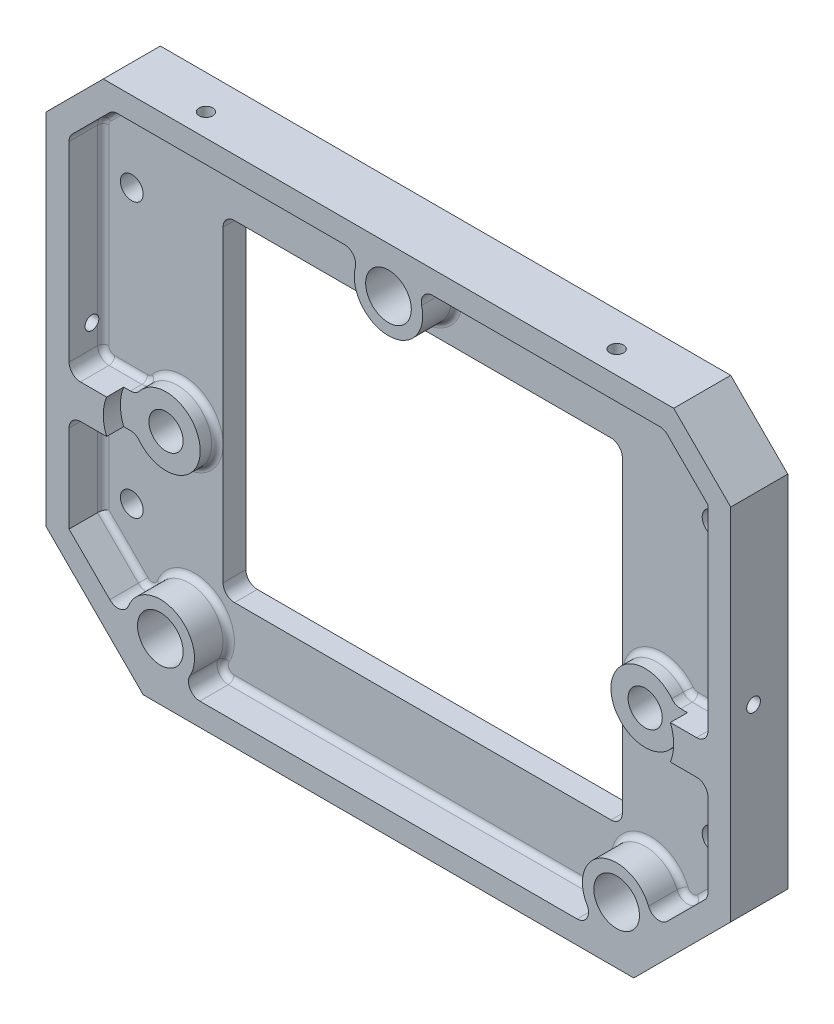
SolidWorks part; units mm, degrees
ref_plane "前视基准面" through (0, 0, 0) normal (0, 0, 1) x (1, 0, 0)
ref_plane "上视基准面" through (0, 0, 0) normal (0, 1, 0) x (1, 0, 0)
ref_plane "右视基准面" through (0, 0, 0) normal (1, 0, 0) x (0, 0, -1)
sketch "草图1" plane through (0, 0, 0) normal (0, 0, 1) x (1, 0, 0)
  line L0 (0, 54.5254) -> (0, -46.9226) construction
  line L1 (77.1188, 0) -> (-86.5987, 0) construction
  line L2 (-30, 25) -> (-18, 25) construction
  line L3 (-18, 25) -> (-18, 1.5) construction
  line L4 (-18, 1.5) -> (-30, 1.5) construction
  line L5 (-30, 1.5) -> (-30, -3.5)
  line L6 (-30, -3.5) -> (-21.5, -12)
  line L7 (-21.5, -12) -> (-15.5, -12)
  line L8 (-15.5, -12) -> (-15.5, 0) construction
  line L9 (-15.5, 0) -> (15.5, 0) construction
  line L10 (-30, 25) -> (-30, 28)
  line L11 (-25, 33) -> (25, 33)
  line L12 (-17.5, 24) -> (-17.5, -3)
  line L13 (-16.5, -4) -> (16.5, -4)
  line L14 (16.5, 25) -> (-16.5, 25)
  line L15 (15.5, -12) -> (15.5, 0) construction
  line L16 (21.5, -12) -> (15.5, -12)
  line L17 (18, 1.5) -> (30, 1.5) construction
  line L18 (30, 1.5) -> (30, -3.5)
  line L19 (18, 25) -> (18, 1.5) construction
  line L20 (30, 25) -> (30, 28)
  line L21 (17.5, 24) -> (17.5, -3)
  line L22 (18, 25) -> (30, 25) construction
  line L23 (21.5, -12) -> (30, -3.5)
  line L24 (-30, 28) -> (-25, 33)
  line L25 (30, 28) -> (25, 33)
  line L26 (-30, 25) -> (-30, 1.5)
  line L27 (30, 25) -> (30, 1.5)
  line L28 (-15.5, -12) -> (15.5, -12)
  circle A0 centre (20, -7) radius 2
  circle A1 centre (12.5, 29) radius 2 construction
  circle A2 centre (0, 29) radius 2
  circle A3 centre (-20, -7) radius 2
  circle A4 centre (-12.5, 29) radius 2 construction
  circle A5 centre (24, 27.5) radius 1 construction
  circle A6 centre (24, -1) radius 1 construction
  circle A7 centre (-24, 27.5) radius 1 construction
  circle A8 centre (-24, -1) radius 1 construction
  circle A9 centre (-21, 7.5) radius 6 construction
  circle A10 centre (-21, 7.5) radius 1.5
  circle A11 centre (21, 7.5) radius 1.5
  arc A12 (-17.5, -3) -> (-16.5, -4) centre (-16.5, -3) ccw
  arc A13 (17.5, -3) -> (16.5, -4) centre (16.5, -3) cw
  arc A14 (17.5, 24) -> (16.5, 25) centre (16.5, 24) ccw
  arc A15 (-17.5, 24) -> (-16.5, 25) centre (-16.5, 24) cw
  point P36 (0, 36)
  point P37 (-30, 33)
  point P40 (0, 0)
  point P41 (0, 0)
  point P48 (30, 33)
  point P50 (0, 25)
  point P63 (-17.5, -4)
  point P66 (17.5, -4)
  point P69 (17.5, 25)
  point P72 (-17.5, 25)
  dimension "D1" = 4
  dimension "D2" = 4
  dimension "D3" = 4
  dimension "D10" = 2
  dimension "D11" = 2
  dimension "D22" = 12
  dimension "D25" = 3
  dimension "D28" = 1
  dimension "D30" = 7.5
  dimension "D4" = 28.5
  dimension "D5" = 21
  dimension "D6" = 40
  dimension "D7" = 25
  dimension "D8" = 7
  dimension "D9" = 1
  dimension "D12" = 29
  dimension "D13" = 15.5
  dimension "D14" = 2.5
  dimension "D15" = 6
  dimension "D16" = 2.5
  dimension "D17" = 8
  dimension "D18" = 6
  dimension "D19" = 6
  dimension "D20" = 12
  dimension "D21" = 8
  dimension "D23" = 45
  dimension "D24" = 35
  dimension "D29" = 30
extrude "凸台-拉伸1" add sketch "草图1" along normal blind 2
sketch "Sketch1" plane through (0, 0, 2) normal (0, 0, 1) x (1, 0, 0)
  line L0 (-30, 28) -> (-30, -3.5) construction
  line L1 (-30, -3.5) -> (-21.5, -12) construction
  line L2 (-21.5, -12) -> (21.5, -12) construction
  line L3 (21.5, -12) -> (30, -3.5) construction
  line L4 (30, -3.5) -> (30, 28) construction
  line L5 (30, 28) -> (25, 33) construction
  line L6 (25, 33) -> (-25, 33) construction
  line L7 (-25, 33) -> (-30, 28) construction
  line L8 (-30, 28) -> (-30, -3.5)
  line L9 (-30, -3.5) -> (-21.5, -12)
  line L10 (-21.5, -12) -> (21.5, -12)
  line L11 (21.5, -12) -> (30, -3.5)
  line L12 (30, -3.5) -> (30, 28)
  line L13 (30, 28) -> (25, 33)
  line L14 (25, 33) -> (-25, 33)
  line L15 (-25, 33) -> (-30, 28)
  line L16 (-24.1716, 31) -> (-28, 27.1716)
  line L17 (-28, 27.1716) -> (-28, 9)
  line L18 (-28, -2.6716) -> (-24.4293, -6.2423)
  line L19 (-16.5359, -10) -> (16.5359, -10)
  line L21 (28, -2.6716) -> (28, 6)
  line L22 (28, 27.1716) -> (24.1716, 31)
  line L23 (24.1716, 31) -> (3.873, 31)
  line L24 (-3.873, 31) -> (-24.1716, 31)
  line L25 (24.1716, 31) -> (-24.1716, 31) construction
  line L26 (24.4293, -6.2423) -> (28, -2.6716)
  line L27 (20.6716, -10) -> (28, -2.6716) construction
  line L28 (-20.6716, -10) -> (20.6716, -10) construction
  line L30 (-28, -2.6716) -> (-20.6716, -10) construction
  line L31 (-21, 7.5) -> (5.3284, 7.5) construction
  line L32 (-28, 9) -> (-23.5981, 9)
  line L33 (-28, 6) -> (-23.5981, 6)
  line L34 (23.5981, 9) -> (28, 9)
  line L35 (23.5981, 6) -> (28, 6)
  line L36 (28, 9) -> (28, 27.1716)
  line L37 (28, -2.6716) -> (28, 27.1716) construction
  line L38 (-28, 6) -> (-28, -2.6716)
  line L39 (-28, 27.1716) -> (-28, -2.6716) construction
  arc A0 (-2.9047, 29.75) -> (2.9047, 29.75) centre (0, 29) ccw
  arc A1 (-17.4019, -8.5) -> (-22.7916, -5.9014) centre (-20, -7) ccw
  arc A2 (22.7916, -5.9014) -> (17.4019, -8.5) centre (20, -7) ccw
  arc A3 (23.5981, 9) -> (23.5981, 6) centre (21, 7.5) ccw
  arc A4 (-23.5981, 6) -> (-23.5981, 9) centre (-21, 7.5) ccw
  arc A5 (16.5359, -10) -> (17.4019, -8.5) centre (16.5359, -9) ccw
  arc A6 (-16.5359, -10) -> (-17.4019, -8.5) centre (-16.5359, -9) cw
  arc A7 (-24.4293, -6.2423) -> (-22.7916, -5.9014) centre (-23.7221, -5.5352) ccw
  arc A8 (3.873, 31) -> (2.9047, 29.75) centre (3.873, 30) ccw
  arc A9 (-2.9047, 29.75) -> (-3.873, 31) centre (-3.873, 30) ccw
  arc A10 (24.4293, -6.2423) -> (22.7916, -5.9014) centre (23.7221, -5.5352) cw
  point P45 (-2.2361, 31)
  circle M29 centre (-20, -7) radius 2
  circle M30 centre (0, 29) radius 2
  circle M31 centre (20, -7) radius 2
  line M32 (-21.5, -12) -> (21.5, -12)
  line M33 (21.5, -12) -> (30, -3.5)
  line M34 (30, -3.5) -> (30, 28)
  line M35 (30, 28) -> (25, 33)
  line M36 (25, 33) -> (-25, 33)
  line M37 (-25, 33) -> (-30, 28)
  line M38 (-30, 28) -> (-30, -3.5)
  line M39 (-30, -3.5) -> (-21.5, -12)
  circle M44 centre (-21, 7.5) radius 1.5
  circle M45 centre (21, 7.5) radius 1.5
  dimension "D1" = 6
  dimension "D2" = 6
  dimension "D3" = 6
  dimension "D4" = 6
  dimension "D5" = 6
  dimension "D7" = 1
  dimension "D8" = 1
  dimension "D6" = 2
  dimension "D9" = 3
extrude "Boss-Extrude1" add sketch "Sketch1" along normal blind 3 contours L26 A10 A2 A5 L19 A6 A1 A7 L18 L17 L16 L24 A9 A0 A8 L23 L22 L21 M39 M32 M33 M34 M35 M36 M37 M38 M29 M31 M30 | A4 M44 | A3 M45 region at (-26.9697, 29.9697, 2)
sketch "Sketch2" plane through (0, 0, 5) normal (0, 0, 1) x (1, 0, 0)
  line L8 (-30, -3.5) -> (-21.5, -12)
  line L9 (-30, -3.5) -> (-21.5, -12)
  line L10 (-21.5, -12) -> (21.5, -12)
  line L11 (-21.5, -12) -> (21.5, -12)
  line L12 (21.5, -12) -> (30, -3.5)
  line L13 (21.5, -12) -> (30, -3.5)
  line L14 (30, -3.5) -> (30, 28)
  line L15 (30, -3.5) -> (30, 28)
  line L16 (30, 28) -> (25, 33)
  line L17 (30, 28) -> (25, 33)
  line L18 (25, 33) -> (-25, 33)
  line L19 (25, 33) -> (-25, 33)
  line L20 (-25, 33) -> (-30, 28)
  line L21 (-25, 33) -> (-30, 28)
  line L22 (-30, 28) -> (-30, -3.5)
  line L23 (-30, 28) -> (-30, -3.5)
  line L24 (-30, -3.5) -> (-21.5, -12)
  line L25 (-30, -3.5) -> (-21.5, -12)
  line L26 (-21.5, -12) -> (21.5, -12)
  line L27 (-21.5, -12) -> (21.5, -12)
  line L28 (21.5, -12) -> (30, -3.5)
  line L29 (21.5, -12) -> (30, -3.5)
  line L30 (30, -3.5) -> (30, 28)
  line L31 (30, -3.5) -> (30, 28)
  line L32 (30, 28) -> (25, 33)
  line L33 (30, 28) -> (25, 33)
  line L34 (25, 33) -> (-25, 33)
  line L35 (25, 33) -> (-25, 33)
  line L36 (-25, 33) -> (-30, 28)
  line L37 (-25, 33) -> (-30, 28)
  line L38 (-30, 28) -> (-30, -3.5)
  line L39 (-30, 28) -> (-30, -3.5)
  dimension "D1" = 0
  dimension "D2" = 0
sketch "Sketch3" plane through (0, 0, 0) normal (0, 0, -1) x (-1, 0, 0)
  line L0 (0, -4.2309) -> (0, 20.8684) construction
  circle A0 centre (-25.5, 23) radius 1
  circle A1 centre (-25.5, -1) radius 1
  circle A2 centre (25.5, -1) radius 1
  circle A3 centre (25.5, 23) radius 1
  dimension "D1" = 24
  dimension "D3" = 2
  dimension "D4" = 2
  dimension "D2" = 25.5
  dimension "D5" = 1
fillet "Fillet2" radius 1 12 edges at (28, -2.6716, 3.5) (24.1716, 31, 3.5) (-28, 27.1716, 3.5) (-24.1716, 31, 3.5) (23.5981, 9, 3.5) (28, 9, 3.5) (28, 6, 3.5) (23.5981, 6, 3.5) (-28, 6, 3.5) (-23.5981, 6, 3.5) (-23.5981, 9, 3.5) (-28, 9, 3.5)
fillet "Fillet3" radius 0.5 38 edges at (24.14, 30.9239, 2) (26.2322, 28.9393, 2) (28, 1.3713, 2) (27.9239, -2.64, 2) (26.0682, -4.6034, 2) (23.5183, -6.5142, 2) (18.6971, -4.2977, 2) (17.4019, -9.5, 2) (0, -10, 2) (-17.4019, -9.5, 2) (-18.6971, -4.2977, 2) (-23.5183, -6.5142, 2) (-26.2146, -4.4569, 2) (-28, 18.3787, 2) (-27.9239, 27.14, 2) (-26.0858, 29.0858, 2) (-24.14, 30.9239, 2) (-13.8152, 31, 2) (-3.0824, 30.6124, 2) (0, 26, 2) (3.0824, 30.6124, 2) (-18, 7.5, 2) (18, 7.5, 2) (13.8152, 31, 2) (28, 18.5858, 2) (27.7071, 9.2929, 2) (25.5612, 9, 2) (23.6895, 9.0986, 2) (27.7071, 5.7071, 2) (25.5612, 6, 2) (23.6895, 5.9014, 2) (-28, 1.1642, 2) (-27.7071, 5.7071, 2) (-25.5612, 6, 2) (-23.6895, 5.9014, 2) (-23.6895, 9.0986, 2) (-25.5612, 9, 2) (-27.7071, 9.2929, 2)
sketch "Sketch4" plane through (0, 0, 5) normal (0, 0, 1) x (1, 0, 0)
  circle A0 centre (-21, 7.5) radius 4
  circle A1 centre (21, 7.5) radius 4
  dimension "D1" = 8
  dimension "D2" = 8
extrude "Cut-Extrude3" cut sketch "Sketch4" against normal blind 1.5
sketch "Sketch5" plane through (0, 33, 0) normal (0, 1, 0) x (1, 0, 0)
  line L1 (0, 0) -> (0, -7.4325) construction
  line L2 (-21.5, -5) -> (21.5, -5) construction
  circle A0 centre (-18, -3) radius 0.6
  circle A1 centre (18, -3) radius 0.6
  dimension "D2" = 1.2
  dimension "D1" = 36
  dimension "D3" = 2
extrude "Cut-Extrude4" cut sketch "Sketch5" against normal blind 2.5
extrude "Cut-Extrude5" cut sketch "Sketch3" against normal blind 10
sketch "Sketch6" plane through (30, 0, 0) normal (1, 0, 0) x (0, 0, -1)
  line L0 (-5, -3.5) -> (-5, 28) construction
  circle A0 centre (-3, 12) radius 0.6
  dimension "D3" = 1.2
  dimension "D1" = 12
  dimension "D2" = 2
extrude "Cut-Extrude6" cut sketch "Sketch6" against normal blind 65
